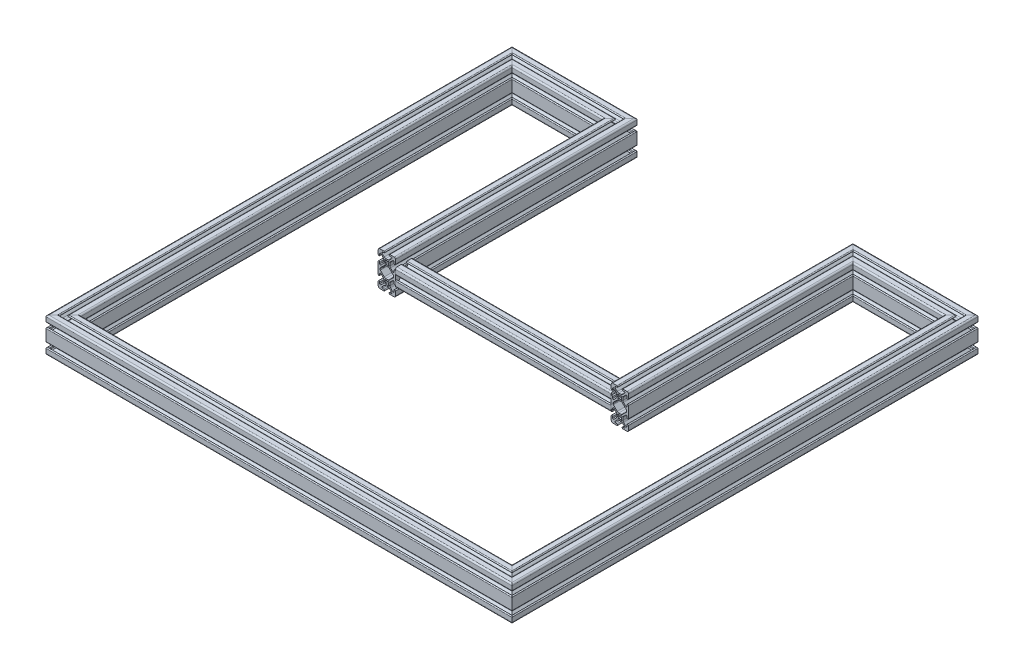
SolidWorks part; units mm, degrees
ref_plane "Front Plane" through (0, 0, 0) normal (0, 0, 1) x (1, 0, 0)
ref_plane "Top Plane" through (0, 0, 0) normal (0, 1, 0) x (1, 0, 0)
ref_plane "Right Plane" through (0, 0, 0) normal (1, 0, 0) x (0, 0, -1)
sketch "Sketch2" plane through (0, 0, 0) normal (0, 1, 0) x (1, 0, 0)
  line L0 (-171.45, 330.2) -> (-330.2, 330.2)
  line L1 (330.2, -330.2) -> (-330.2, -330.2)
  line L2 (330.2, -330.2) -> (330.2, 330.2)
  line L3 (330.2, 330.2) -> (171.45, 330.2)
  line L4 (-330.2, -330.2) -> (-330.2, 330.2)
  line L5 (330.2, -330.2) -> (-330.2, 330.2) construction
  line L6 (330.2, 330.2) -> (-330.2, -330.2) construction
  line L8 (-171.45, 330.2) -> (-171.45, 0)
  line L9 (-171.45, 0) -> (171.45, 0)
  line L10 (171.45, 330.2) -> (171.45, 0)
  point P0 (0, 0)
  point P10 (0, 0)
  point P11 (0, 0)
  dimension "D1" = 660.4
  dimension "D2" = 660.4
  dimension "D3" = 158.75
other "8020 1020-S(2)"
ref_plane "Plane3" through (-330.2, 0, 330.2) normal (0, 0, -1) x (-1, 0, 0)
sketch "Sketch1" plane through (-330.2, 0, 330.2) normal (0, 0, -1) x (-1, 0, 0)
  line L0 (2.2319, -14.0405) -> (2.8605, -14.6692)
  line L1 (1.9692, -15.5605) -> (1.3405, -14.9319)
  line L2 (-1.3405, -14.9319) -> (-1.9692, -15.5605)
  line L3 (-2.8605, -14.6692) -> (-2.2319, -14.0405)
  line L4 (-2.2319, -11.3595) -> (-2.8605, -10.7308)
  line L5 (-1.9692, -9.8395) -> (-1.3405, -10.4681)
  line L6 (1.3405, -10.4681) -> (1.9692, -9.8395)
  line L7 (2.8605, -10.7308) -> (2.2319, -11.3595)
  line L8 (2.8605, 14.6692) -> (2.2319, 14.0405)
  line L9 (2.2319, 11.3595) -> (2.8605, 10.7308)
  line L10 (1.9692, 9.8395) -> (1.3405, 10.4681)
  line L11 (-1.3405, 10.4681) -> (-1.9692, 9.8395)
  line L12 (-2.8605, 10.7308) -> (-2.2319, 11.3595)
  line L13 (-2.2319, 14.0405) -> (-2.8605, 14.6692)
  line L14 (-1.9692, 15.5605) -> (-1.3405, 14.9319)
  line L15 (1.3405, 14.9319) -> (1.9692, 15.5605)
  line L16 (-10.033, -0.4522) -> (-10.033, 0.4522)
  line L17 (-9.5718, 1.5658) -> (-3.8846, 7.2529)
  line L18 (-1.6396, 8.1828) -> (1.6396, 8.1828)
  line L19 (3.8846, 7.2529) -> (9.5718, 1.5658)
  line L20 (10.033, 0.4522) -> (10.033, -0.4522)
  line L21 (9.5718, -1.5658) -> (3.8846, -7.2529)
  line L22 (1.6396, -8.1828) -> (-1.6396, -8.1828)
  line L23 (-3.8846, -7.2529) -> (-9.5718, -1.5658)
  line L24 (10.4902, 8.3439) -> (10.4902, 6.2251)
  line L25 (8.7558, 5.5067) -> (5.4471, 8.8154)
  line L26 (4.5172, 11.0604) -> (4.5172, 14.3396)
  line L27 (5.4471, 16.5846) -> (8.7558, 19.8933)
  line L28 (10.4902, 19.1749) -> (10.4902, 17.0561)
  line L29 (12.7, 17.0561) -> (12.7, 23.2918)
  line L30 (10.5918, 25.4) -> (4.3561, 25.4)
  line L31 (4.3561, 23.1902) -> (6.4749, 23.1902)
  line L32 (7.1933, 21.4558) -> (3.8846, 18.1471)
  line L33 (1.6396, 17.2172) -> (-1.6396, 17.2172)
  line L34 (-3.8846, 18.1471) -> (-7.1933, 21.4558)
  line L35 (-6.4749, 23.1902) -> (-4.3561, 23.1902)
  line L36 (-4.3561, 25.4) -> (-10.5918, 25.4)
  line L37 (-12.7, 23.2918) -> (-12.7, 17.0561)
  line L38 (-10.4902, 17.0561) -> (-10.4902, 19.1749)
  line L39 (-8.7558, 19.8933) -> (-5.4471, 16.5846)
  line L40 (-4.5172, 14.3396) -> (-4.5172, 11.0604)
  line L41 (-5.4471, 8.8154) -> (-8.7558, 5.5067)
  line L42 (-10.4902, 6.2251) -> (-10.4902, 8.3439)
  line L43 (-12.7, 8.3439) -> (-12.7, -8.3439)
  line L44 (-10.4902, -8.3439) -> (-10.4902, -6.2251)
  line L45 (-8.7558, -5.5067) -> (-5.4471, -8.8154)
  line L46 (-4.5172, -11.0604) -> (-4.5172, -14.3396)
  line L47 (-5.4471, -16.5846) -> (-8.7558, -19.8933)
  line L48 (-10.4902, -19.1749) -> (-10.4902, -17.0561)
  line L49 (-12.7, -17.0561) -> (-12.7, -23.2918)
  line L50 (-10.5918, -25.4) -> (-4.3561, -25.4)
  line L51 (-4.3561, -23.1902) -> (-6.4749, -23.1902)
  line L52 (-7.1933, -21.4558) -> (-3.8846, -18.1471)
  line L53 (-1.6396, -17.2172) -> (1.6396, -17.2172)
  line L54 (3.8846, -18.1471) -> (7.1933, -21.4558)
  line L55 (6.4749, -23.1902) -> (4.3561, -23.1902)
  line L56 (4.3561, -25.4) -> (10.5918, -25.4)
  line L57 (12.7, -23.2918) -> (12.7, -17.0561)
  line L58 (10.4902, -17.0561) -> (10.4902, -19.1749)
  line L59 (8.7558, -19.8933) -> (5.4471, -16.5846)
  line L60 (4.5172, -14.3396) -> (4.5172, -11.0604)
  line L61 (5.4471, -8.8154) -> (8.7558, -5.5067)
  line L62 (10.4902, -6.2251) -> (10.4902, -8.3439)
  line L63 (12.7, -8.3439) -> (12.7, 8.3439)
  arc A0 (1.9692, -15.5605) -> (2.8605, -14.6692) centre (2.4696, -15.1696) ccw
  arc A1 (-1.3405, -14.9319) -> (1.3405, -14.9319) centre (0, -12.7) ccw
  arc A2 (-2.8605, -14.6692) -> (-1.9692, -15.5605) centre (-2.4696, -15.1696) ccw
  arc A3 (-2.2319, -11.3595) -> (-2.2319, -14.0405) centre (0, -12.7) ccw
  arc A4 (-1.9692, -9.8395) -> (-2.8605, -10.7308) centre (-2.4696, -10.2304) ccw
  arc A5 (1.3405, -10.4681) -> (-1.3405, -10.4681) centre (0, -12.7) ccw
  arc A6 (2.8605, -10.7308) -> (1.9692, -9.8395) centre (2.4696, -10.2304) ccw
  arc A7 (2.2319, -14.0405) -> (2.2319, -11.3595) centre (0, -12.7) ccw
  arc A8 (2.2319, 11.3595) -> (2.2319, 14.0405) centre (0, 12.7) ccw
  arc A9 (1.9692, 9.8395) -> (2.8605, 10.7308) centre (2.4696, 10.2304) ccw
  arc A10 (-1.3405, 10.4681) -> (1.3405, 10.4681) centre (0, 12.7) ccw
  arc A11 (-2.8605, 10.7308) -> (-1.9692, 9.8395) centre (-2.4696, 10.2304) ccw
  arc A12 (-2.2319, 14.0405) -> (-2.2319, 11.3595) centre (0, 12.7) ccw
  arc A13 (-1.9692, 15.5605) -> (-2.8605, 14.6692) centre (-2.4696, 15.1696) ccw
  arc A14 (1.3405, 14.9319) -> (-1.3405, 14.9319) centre (0, 12.7) ccw
  arc A15 (2.8605, 14.6692) -> (1.9692, 15.5605) centre (2.4696, 15.1696) ccw
  arc A16 (-10.033, -0.4522) -> (-9.5718, -1.5658) centre (-8.4582, -0.4522) ccw
  arc A17 (-9.5718, 1.5658) -> (-10.033, 0.4522) centre (-8.4582, 0.4522) ccw
  arc A18 (-1.6396, 8.1828) -> (-3.8846, 7.2529) centre (-1.6396, 5.0078) ccw
  arc A19 (3.8846, 7.2529) -> (1.6396, 8.1828) centre (1.6396, 5.0078) ccw
  arc A20 (10.033, 0.4522) -> (9.5718, 1.5658) centre (8.4582, 0.4522) ccw
  arc A21 (9.5718, -1.5658) -> (10.033, -0.4522) centre (8.4582, -0.4522) ccw
  arc A22 (1.6396, -8.1828) -> (3.8846, -7.2529) centre (1.6396, -5.0078) ccw
  arc A23 (-3.8846, -7.2529) -> (-1.6396, -8.1828) centre (-1.6396, -5.0078) ccw
  arc A24 (12.7, 8.3439) -> (10.4902, 8.3439) centre (11.5951, 8.3439) ccw
  arc A25 (8.7558, 5.5067) -> (10.4902, 6.2251) centre (9.4742, 6.2251) ccw
  arc A26 (4.5172, 11.0604) -> (5.4471, 8.8154) centre (7.6922, 11.0604) ccw
  arc A27 (5.4471, 16.5846) -> (4.5172, 14.3396) centre (7.6922, 14.3396) ccw
  arc A28 (10.4902, 19.1749) -> (8.7558, 19.8933) centre (9.4742, 19.1749) ccw
  arc A29 (10.4902, 17.0561) -> (12.7, 17.0561) centre (11.5951, 17.0561) ccw
  arc A30 (12.7, 23.2918) -> (10.5918, 25.4) centre (10.5918, 23.2918) ccw
  arc A31 (4.3561, 25.4) -> (4.3561, 23.1902) centre (4.3561, 24.2951) ccw
  arc A32 (7.1933, 21.4558) -> (6.4749, 23.1902) centre (6.4749, 22.1742) ccw
  arc A33 (1.6396, 17.2172) -> (3.8846, 18.1471) centre (1.6396, 20.3922) ccw
  arc A34 (-3.8846, 18.1471) -> (-1.6396, 17.2172) centre (-1.6396, 20.3922) ccw
  arc A35 (-6.4749, 23.1902) -> (-7.1933, 21.4558) centre (-6.4749, 22.1742) ccw
  arc A36 (-4.3561, 23.1902) -> (-4.3561, 25.4) centre (-4.3561, 24.2951) ccw
  arc A37 (-10.5918, 25.4) -> (-12.7, 23.2918) centre (-10.5918, 23.2918) ccw
  arc A38 (-12.7, 17.0561) -> (-10.4902, 17.0561) centre (-11.5951, 17.0561) ccw
  arc A39 (-8.7558, 19.8933) -> (-10.4902, 19.1749) centre (-9.4742, 19.1749) ccw
  arc A40 (-4.5172, 14.3396) -> (-5.4471, 16.5846) centre (-7.6922, 14.3396) ccw
  arc A41 (-5.4471, 8.8154) -> (-4.5172, 11.0604) centre (-7.6922, 11.0604) ccw
  arc A42 (-10.4902, 6.2251) -> (-8.7558, 5.5067) centre (-9.4742, 6.2251) ccw
  arc A43 (-10.4902, 8.3439) -> (-12.7, 8.3439) centre (-11.5951, 8.3439) ccw
  arc A44 (-12.7, -8.3439) -> (-10.4902, -8.3439) centre (-11.5951, -8.3439) ccw
  arc A45 (-8.7558, -5.5067) -> (-10.4902, -6.2251) centre (-9.4742, -6.2251) ccw
  arc A46 (-4.5172, -11.0604) -> (-5.4471, -8.8154) centre (-7.6922, -11.0604) ccw
  arc A47 (-5.4471, -16.5846) -> (-4.5172, -14.3396) centre (-7.6922, -14.3396) ccw
  arc A48 (-10.4902, -19.1749) -> (-8.7558, -19.8933) centre (-9.4742, -19.1749) ccw
  arc A49 (-10.4902, -17.0561) -> (-12.7, -17.0561) centre (-11.5951, -17.0561) ccw
  arc A50 (-12.7, -23.2918) -> (-10.5918, -25.4) centre (-10.5918, -23.2918) ccw
  arc A51 (-4.3561, -25.4) -> (-4.3561, -23.1902) centre (-4.3561, -24.2951) ccw
  arc A52 (-7.1933, -21.4558) -> (-6.4749, -23.1902) centre (-6.4749, -22.1742) ccw
  arc A53 (-1.6396, -17.2172) -> (-3.8846, -18.1471) centre (-1.6396, -20.3922) ccw
  arc A54 (3.8846, -18.1471) -> (1.6396, -17.2172) centre (1.6396, -20.3922) ccw
  arc A55 (6.4749, -23.1902) -> (7.1933, -21.4558) centre (6.4749, -22.1742) ccw
  arc A56 (4.3561, -23.1902) -> (4.3561, -25.4) centre (4.3561, -24.2951) ccw
  arc A57 (10.5918, -25.4) -> (12.7, -23.2918) centre (10.5918, -23.2918) ccw
  arc A58 (12.7, -17.0561) -> (10.4902, -17.0561) centre (11.5951, -17.0561) ccw
  arc A59 (8.7558, -19.8933) -> (10.4902, -19.1749) centre (9.4742, -19.1749) ccw
  arc A60 (4.5172, -14.3396) -> (5.4471, -16.5846) centre (7.6922, -14.3396) ccw
  arc A61 (5.4471, -8.8154) -> (4.5172, -11.0604) centre (7.6922, -11.0604) ccw
  arc A62 (10.4902, -6.2251) -> (8.7558, -5.5067) centre (9.4742, -6.2251) ccw
  arc A63 (10.4902, -8.3439) -> (12.7, -8.3439) centre (11.5951, -8.3439) ccw
  point P0 (0, 0)
other "8020 1010-S(1)"
ref_plane "Plane4" through (-171.45, 0, 0) normal (1, 0, 0) x (0, 0, -1)
sketch "Sketch13" plane through (-171.45, 0, 0) normal (1, 0, 0) x (0, 0, -1)
  line L0 (-2.8605, -1.9692) -> (-2.2319, -1.3405)
  line L1 (-2.2319, 1.3405) -> (-2.8605, 1.9692)
  line L2 (-1.9692, 2.8605) -> (-1.3405, 2.2319)
  line L3 (1.3405, 2.2319) -> (1.9692, 2.8605)
  line L4 (2.8605, 1.9692) -> (2.2319, 1.3405)
  line L5 (2.2319, -1.3405) -> (2.8605, -1.9692)
  line L6 (1.9692, -2.8605) -> (1.3405, -2.2319)
  line L7 (-1.3405, -2.2319) -> (-1.9692, -2.8605)
  line L8 (-3.8846, 5.4471) -> (-7.1933, 8.7558)
  line L9 (1.6396, 4.5172) -> (-1.6396, 4.5172)
  line L10 (7.1933, 8.7558) -> (3.8846, 5.4471)
  line L11 (12.7, -10.5918) -> (12.7, -4.3561)
  line L12 (5.4471, 3.8846) -> (8.7558, 7.1933)
  line L13 (4.5172, -1.6396) -> (4.5172, 1.6396)
  line L14 (8.7558, -7.1933) -> (5.4471, -3.8846)
  line L15 (-10.5918, -12.7) -> (-4.3561, -12.7)
  line L16 (3.8846, -5.4471) -> (7.1933, -8.7558)
  line L17 (-1.6396, -4.5172) -> (1.6396, -4.5172)
  line L18 (-7.1933, -8.7558) -> (-3.8846, -5.4471)
  line L19 (-12.7, 10.5918) -> (-12.7, 4.3561)
  line L20 (-5.4471, -3.8846) -> (-8.7558, -7.1933)
  line L21 (-4.5172, 1.6396) -> (-4.5172, -1.6396)
  line L22 (-8.7558, 7.1933) -> (-5.4471, 3.8846)
  line L23 (-10.5918, 12.7) -> (-4.3561, 12.7)
  line L24 (-6.4749, 10.4902) -> (-4.3561, 10.4902)
  line L25 (-10.4902, 6.4749) -> (-10.4902, 4.3561)
  line L26 (-6.4749, -10.4902) -> (-4.3561, -10.4902)
  line L27 (10.4902, -6.4749) -> (10.4902, -4.3561)
  line L28 (4.3561, 12.7) -> (10.5918, 12.7)
  line L29 (4.3561, 10.4902) -> (6.4749, 10.4902)
  line L30 (-10.4902, -4.3561) -> (-10.4902, -6.4749)
  line L31 (-12.7, -4.3561) -> (-12.7, -10.5918)
  line L32 (4.3561, -10.4902) -> (6.4749, -10.4902)
  line L33 (4.3561, -12.7) -> (10.5918, -12.7)
  line L34 (12.7, 4.3561) -> (12.7, 10.5918)
  line L35 (10.4902, 4.3561) -> (10.4902, 6.4749)
  arc A0 (-2.8605, -1.9692) -> (-1.9692, -2.8605) centre (-2.4696, -2.4696) ccw
  arc A1 (-2.2319, 1.3405) -> (-2.2319, -1.3405) centre (0, 0) ccw
  arc A2 (-1.9692, 2.8605) -> (-2.8605, 1.9692) centre (-2.4696, 2.4696) ccw
  arc A3 (1.3405, 2.2319) -> (-1.3405, 2.2319) centre (0, 0) ccw
  arc A4 (2.8605, 1.9692) -> (1.9692, 2.8605) centre (2.4696, 2.4696) ccw
  arc A5 (2.2319, -1.3405) -> (2.2319, 1.3405) centre (0, 0) ccw
  arc A6 (1.9692, -2.8605) -> (2.8605, -1.9692) centre (2.4696, -2.4696) ccw
  arc A7 (-1.3405, -2.2319) -> (1.3405, -2.2319) centre (0, 0) ccw
  arc A8 (-3.8846, 5.4471) -> (-1.6396, 4.5172) centre (-1.6396, 7.6922) ccw
  arc A9 (1.6396, 4.5172) -> (3.8846, 5.4471) centre (1.6396, 7.6922) ccw
  arc A10 (5.4471, 3.8846) -> (4.5172, 1.6396) centre (7.6922, 1.6396) ccw
  arc A11 (4.5172, -1.6396) -> (5.4471, -3.8846) centre (7.6922, -1.6396) ccw
  arc A12 (3.8846, -5.4471) -> (1.6396, -4.5172) centre (1.6396, -7.6922) ccw
  arc A13 (-1.6396, -4.5172) -> (-3.8846, -5.4471) centre (-1.6396, -7.6922) ccw
  arc A14 (-5.4471, -3.8846) -> (-4.5172, -1.6396) centre (-7.6922, -1.6396) ccw
  arc A15 (-4.5172, 1.6396) -> (-5.4471, 3.8846) centre (-7.6922, 1.6396) ccw
  arc A16 (-12.7, -10.5918) -> (-10.5918, -12.7) centre (-10.5918, -10.5918) ccw
  arc A17 (10.5918, -12.7) -> (12.7, -10.5918) centre (10.5918, -10.5918) ccw
  arc A18 (12.7, 10.5918) -> (10.5918, 12.7) centre (10.5918, 10.5918) ccw
  arc A19 (-10.5918, 12.7) -> (-12.7, 10.5918) centre (-10.5918, 10.5918) ccw
  arc A20 (-8.7558, 7.1933) -> (-10.4902, 6.4749) centre (-9.4742, 6.4749) ccw
  arc A21 (-6.4749, 10.4902) -> (-7.1933, 8.7558) centre (-6.4749, 9.4742) ccw
  arc A22 (7.1933, 8.7558) -> (6.4749, 10.4902) centre (6.4749, 9.4742) ccw
  arc A23 (10.4902, 6.4749) -> (8.7558, 7.1933) centre (9.4742, 6.4749) ccw
  arc A24 (8.7558, -7.1933) -> (10.4902, -6.4749) centre (9.4742, -6.4749) ccw
  arc A25 (6.4749, -10.4902) -> (7.1933, -8.7558) centre (6.4749, -9.4742) ccw
  arc A26 (-7.1933, -8.7558) -> (-6.4749, -10.4902) centre (-6.4749, -9.4742) ccw
  arc A27 (-10.4902, -6.4749) -> (-8.7558, -7.1933) centre (-9.4742, -6.4749) ccw
  arc A28 (-4.3561, 10.4902) -> (-4.3561, 12.7) centre (-4.3561, 11.5951) ccw
  arc A29 (4.3561, 12.7) -> (4.3561, 10.4902) centre (4.3561, 11.5951) ccw
  arc A30 (-12.7, 4.3561) -> (-10.4902, 4.3561) centre (-11.5951, 4.3561) ccw
  arc A31 (-10.4902, -4.3561) -> (-12.7, -4.3561) centre (-11.5951, -4.3561) ccw
  arc A32 (-4.3561, -12.7) -> (-4.3561, -10.4902) centre (-4.3561, -11.5951) ccw
  arc A33 (4.3561, -10.4902) -> (4.3561, -12.7) centre (4.3561, -11.5951) ccw
  arc A34 (12.7, -4.3561) -> (10.4902, -4.3561) centre (11.5951, -4.3561) ccw
  arc A35 (10.4902, 4.3561) -> (12.7, 4.3561) centre (11.5951, 4.3561) ccw
  point P0 (0, 0)
other "Trim/Extend2"
other "Trim/Extend3"
other "Trim/Extend4"
other "Trim/Extend5"
